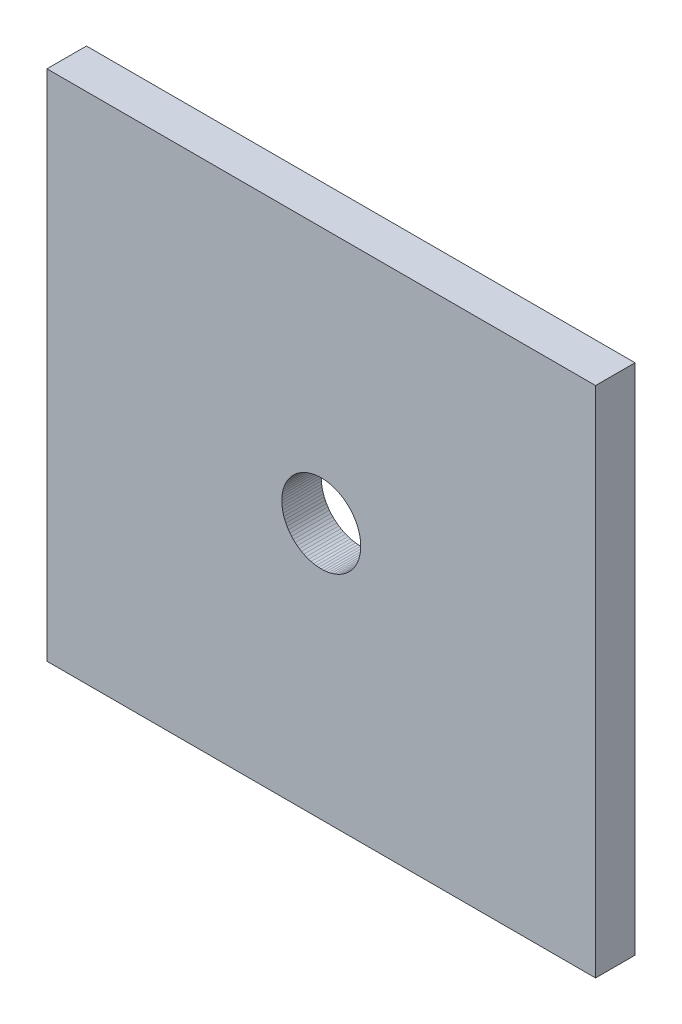
SolidWorks part; units mm, degrees
material "Plain Carbon Steel"
ref_plane "Front Plane" through (0, 0, 0) normal (0, 0, 1) x (1, 0, 0)
ref_plane "Top Plane" through (0, 0, 0) normal (0, 1, 0) x (1, 0, 0)
ref_plane "Right Plane" through (0, 0, 0) normal (1, 0, 0) x (0, 0, -1)
sketch "Model" plane through (0, 0, 0) normal (0, 0, 1) x (1, 0, 0)
  line L0 (1622.0549, -184.7379) -> (1622.2624, -184.485)
  line L1 (1617.643, -186.3984) -> (1617.9686, -186.4305)
  line L2 (1621.5924, -185.2004) -> (1621.8312, -184.9767)
  line L3 (1617.0016, -186.2708) -> (1617.3202, -186.3451)
  line L4 (1620.2091, -186.0606) -> (1620.5071, -185.9255)
  line L5 (1617.9686, -176.4519) -> (1617.643, -176.4839)
  line L6 (1613.8113, -183.6526) -> (1613.9655, -183.9412)
  line L7 (1614.7601, -184.9767) -> (1614.9989, -185.2004)
  line L8 (1617.643, -176.4839) -> (1617.3202, -176.5372)
  line L9 (1613.3917, -182.4166) -> (1613.466, -182.7353)
  line L10 (1615.7957, -177.111) -> (1615.5178, -177.2838)
  line L11 (1613.561, -183.0484) -> (1613.6763, -183.3546)
  line L12 (1621.5924, -177.682) -> (1621.3395, -177.4744)
  line L13 (1619.2711, -176.5372) -> (1618.9483, -176.4839)
  line L14 (1616.3822, -176.8218) -> (1616.0842, -176.9568)
  line L15 (1614.9989, -177.682) -> (1614.7601, -177.9056)
  line L16 (1617.3202, -186.3451) -> (1617.643, -186.3984)
  line L17 (1613.3064, -181.1142) -> (1613.2957, -181.4412)
  line L18 (1614.9989, -185.2004) -> (1615.2519, -185.4079)
  line L19 (1614.7601, -177.9056) -> (1614.5365, -178.1444)
  line L20 (1614.5365, -184.7379) -> (1614.7601, -184.9767)
  line L21 (1616.0842, -185.9255) -> (1616.3822, -186.0606)
  line L22 (1613.6763, -179.5278) -> (1613.561, -179.834)
  line L23 (1615.5178, -185.5985) -> (1615.7957, -185.7713)
  line L24 (1616.6885, -176.7065) -> (1616.3822, -176.8218)
  line L25 (1613.561, -179.834) -> (1613.466, -180.1471)
  line L26 (1618.2957, -176.4412) -> (1617.9686, -176.4519)
  line L27 (1613.6763, -183.3546) -> (1613.8113, -183.6526)
  line L28 (1614.5365, -178.1444) -> (1614.3289, -178.3974)
  line L29 (1620.2091, -176.8218) -> (1619.9029, -176.7065)
  line L30 (1618.6227, -176.4519) -> (1618.2957, -176.4412)
  line L31 (1621.0735, -177.2838) -> (1620.7957, -177.111)
  line L32 (1653.0457, -148.9412) -> (1653.0457, -213.9412)
  line L33 (1583.5457, -148.9412) -> (1653.0457, -148.9412)
  line L34 (1583.5457, -213.9412) -> (1583.5457, -148.9412)
  line L35 (1653.0457, -213.9412) -> (1583.5457, -213.9412)
  line L36 (1616.6885, -186.1758) -> (1617.0016, -186.2708)
  line L37 (1616.3822, -186.0606) -> (1616.6885, -186.1758)
  line L38 (1615.7957, -185.7713) -> (1616.0842, -185.9255)
  line L39 (1615.2519, -185.4079) -> (1615.5178, -185.5985)
  line L40 (1614.3289, -184.485) -> (1614.5365, -184.7379)
  line L41 (1614.1383, -184.219) -> (1614.3289, -184.485)
  line L42 (1613.9655, -183.9412) -> (1614.1383, -184.219)
  line L43 (1613.466, -182.7353) -> (1613.561, -183.0484)
  line L44 (1613.3384, -182.0938) -> (1613.3917, -182.4166)
  line L45 (1613.3064, -181.7682) -> (1613.3384, -182.0938)
  line L46 (1613.2957, -181.4412) -> (1613.3064, -181.7682)
  line L47 (1613.3384, -180.7885) -> (1613.3064, -181.1142)
  line L48 (1613.3917, -180.4657) -> (1613.3384, -180.7885)
  line L49 (1613.466, -180.1471) -> (1613.3917, -180.4657)
  line L50 (1613.8113, -179.2297) -> (1613.6763, -179.5278)
  line L51 (1613.9655, -178.9412) -> (1613.8113, -179.2297)
  line L52 (1614.1383, -178.6633) -> (1613.9655, -178.9412)
  line L53 (1614.3289, -178.3974) -> (1614.1383, -178.6633)
  line L54 (1615.2519, -177.4744) -> (1614.9989, -177.682)
  line L55 (1615.5178, -177.2838) -> (1615.2519, -177.4744)
  line L56 (1616.0842, -176.9568) -> (1615.7957, -177.111)
  line L57 (1617.0016, -176.6115) -> (1616.6885, -176.7065)
  line L58 (1617.3202, -176.5372) -> (1617.0016, -176.6115)
  line L59 (1618.9483, -176.4839) -> (1618.6227, -176.4519)
  line L60 (1619.5898, -176.6115) -> (1619.2711, -176.5372)
  line L61 (1619.9029, -176.7065) -> (1619.5898, -176.6115)
  line L62 (1620.5071, -176.9568) -> (1620.2091, -176.8218)
  line L63 (1620.7957, -177.111) -> (1620.5071, -176.9568)
  line L64 (1621.3395, -177.4744) -> (1621.0735, -177.2838)
  line L65 (1621.8312, -177.9056) -> (1621.5924, -177.682)
  line L66 (1622.0549, -178.1444) -> (1621.8312, -177.9056)
  line L67 (1622.2624, -178.3974) -> (1622.0549, -178.1444)
  line L68 (1622.453, -178.6633) -> (1622.2624, -178.3974)
  line L69 (1622.6258, -178.9412) -> (1622.453, -178.6633)
  line L70 (1622.78, -179.2297) -> (1622.6258, -178.9412)
  line L71 (1622.9151, -179.5278) -> (1622.78, -179.2297)
  line L72 (1623.0303, -179.834) -> (1622.9151, -179.5278)
  line L73 (1623.1253, -180.1471) -> (1623.0303, -179.834)
  line L74 (1623.1996, -180.4657) -> (1623.1253, -180.1471)
  line L75 (1623.2529, -180.7885) -> (1623.1996, -180.4657)
  line L76 (1623.285, -181.1142) -> (1623.2529, -180.7885)
  line L77 (1623.2957, -181.4412) -> (1623.285, -181.1142)
  line L78 (1623.285, -181.7682) -> (1623.2957, -181.4412)
  line L79 (1623.2529, -182.0938) -> (1623.285, -181.7682)
  line L80 (1623.1996, -182.4166) -> (1623.2529, -182.0938)
  line L81 (1623.1253, -182.7353) -> (1623.1996, -182.4166)
  line L82 (1623.0303, -183.0484) -> (1623.1253, -182.7353)
  line L83 (1622.9151, -183.3546) -> (1623.0303, -183.0484)
  line L84 (1622.78, -183.6526) -> (1622.9151, -183.3546)
  line L85 (1622.6258, -183.9412) -> (1622.78, -183.6526)
  line L86 (1622.453, -184.219) -> (1622.6258, -183.9412)
  line L87 (1622.2624, -184.485) -> (1622.453, -184.219)
  line L88 (1621.8312, -184.9767) -> (1622.0549, -184.7379)
  line L89 (1621.3395, -185.4079) -> (1621.5924, -185.2004)
  line L90 (1621.0735, -185.5985) -> (1621.3395, -185.4079)
  line L91 (1620.7957, -185.7713) -> (1621.0735, -185.5985)
  line L92 (1620.5071, -185.9255) -> (1620.7957, -185.7713)
  line L93 (1619.9029, -186.1758) -> (1620.2091, -186.0606)
  line L94 (1619.5898, -186.2708) -> (1619.9029, -186.1758)
  line L95 (1619.2711, -186.3451) -> (1619.5898, -186.2708)
  line L96 (1618.9483, -186.3984) -> (1619.2711, -186.3451)
  line L97 (1618.6227, -186.4305) -> (1618.9483, -186.3984)
  line L98 (1618.2957, -186.4412) -> (1618.6227, -186.4305)
  line L99 (1617.9686, -186.4305) -> (1618.2957, -186.4412)
  line L100 (1610.0539, -203.9412) -> (1626.5374, -203.9412)
  line L101 (1610.0539, -202.9412) -> (1610.0539, -194.3253)
  line L102 (1610.0539, -194.3253) -> (1612.0895, -194.3253)
  line L103 (1612.0895, -194.3253) -> (1612.9574, -194.3971)
  line L104 (1612.9574, -194.3971) -> (1613.6879, -194.6125)
  line L105 (1613.6879, -194.6125) -> (1614.1749, -194.9247)
  line L106 (1614.1749, -194.9247) -> (1614.2967, -195.0995)
  line L107 (1614.2967, -195.0995) -> (1614.3373, -195.2868)
  line L108 (1614.3373, -195.2868) -> (1614.3373, -201.9797)
  line L109 (1614.3373, -201.9797) -> (1614.2967, -202.1724)
  line L110 (1614.2967, -202.1724) -> (1614.1749, -202.3512)
  line L111 (1614.1749, -202.3512) -> (1613.6879, -202.6665)
  line L112 (1613.6879, -202.6665) -> (1612.9761, -202.8725)
  line L113 (1612.9761, -202.8725) -> (1612.0895, -202.9412)
  line L114 (1612.0895, -202.9412) -> (1610.0539, -202.9412)
  line L115 (1610.0539, -194.3253) -> (1610.0539, -202.9412)
  line L116 (1610.0539, -202.9412) -> (1612.0895, -202.9412)
  line L117 (1612.0895, -202.9412) -> (1612.9761, -202.8725)
  line L118 (1612.9761, -202.8725) -> (1613.6879, -202.6665)
  line L119 (1613.6879, -202.6665) -> (1614.1749, -202.3512)
  line L120 (1614.1749, -202.3512) -> (1614.2967, -202.1724)
  line L121 (1614.2967, -202.1724) -> (1614.3373, -201.9797)
  line L122 (1614.3373, -201.9797) -> (1614.3373, -195.2868)
  line L123 (1614.3373, -195.2868) -> (1614.2967, -195.0995)
  line L124 (1614.2967, -195.0995) -> (1614.1749, -194.9247)
  line L125 (1614.1749, -194.9247) -> (1613.6879, -194.6125)
  line L126 (1613.6879, -194.6125) -> (1612.9574, -194.3971)
  line L127 (1612.9574, -194.3971) -> (1612.0895, -194.3253)
  line L128 (1612.0895, -194.3253) -> (1610.0539, -194.3253)
  line L129 (1616.0479, -202.9412) -> (1616.0479, -198.5455)
  line L130 (1616.0479, -198.5455) -> (1618.0834, -198.5455)
  line L131 (1618.0834, -198.5455) -> (1619.1979, -198.6828)
  line L132 (1619.1979, -198.6828) -> (1619.8691, -198.8951)
  line L133 (1619.8691, -198.8951) -> (1620.2157, -199.1636)
  line L134 (1620.2157, -199.1636) -> (1620.3312, -199.4696)
  line L135 (1620.3312, -199.4696) -> (1620.3312, -201.9796)
  line L136 (1620.3312, -201.9796) -> (1620.2898, -202.177)
  line L137 (1620.2898, -202.177) -> (1620.1657, -202.3573)
  line L138 (1620.1657, -202.3573) -> (1619.6693, -202.6664)
  line L139 (1619.6693, -202.6664) -> (1618.9481, -202.8725)
  line L140 (1618.9481, -202.8725) -> (1618.0834, -202.9412)
  line L141 (1618.0834, -202.9412) -> (1616.0479, -202.9412)
  line L142 (1616.0479, -194.3253) -> (1616.0479, -202.9412)
  line L143 (1616.0479, -202.9412) -> (1618.0834, -202.9412)
  line L144 (1618.0834, -202.9412) -> (1618.9481, -202.8725)
  line L145 (1618.9481, -202.8725) -> (1619.6693, -202.6665)
  line L146 (1619.6693, -202.6665) -> (1620.1657, -202.3574)
  line L147 (1620.1657, -202.3574) -> (1620.2898, -202.1771)
  line L148 (1620.2898, -202.1771) -> (1620.3312, -201.9797)
  line L149 (1620.3312, -201.9797) -> (1620.3312, -199.4698)
  line L150 (1620.3312, -199.4698) -> (1620.2157, -199.164)
  line L151 (1620.2157, -199.164) -> (1619.8691, -198.8955)
  line L152 (1619.8691, -198.8955) -> (1619.1979, -198.6832)
  line L153 (1619.1979, -198.6832) -> (1618.0834, -198.5459)
  line L154 (1618.0834, -198.5459) -> (1619.1854, -198.4179)
  line L155 (1619.1854, -198.4179) -> (1619.8691, -198.2087)
  line L156 (1619.8691, -198.2087) -> (1620.2157, -197.9309)
  line L157 (1620.2157, -197.9309) -> (1620.3312, -197.6218)
  line L158 (1620.3312, -197.6218) -> (1620.3312, -195.2868)
  line L159 (1620.3312, -195.2868) -> (1620.2898, -195.0995)
  line L160 (1620.2898, -195.0995) -> (1620.1657, -194.9247)
  line L161 (1620.1657, -194.9247) -> (1619.6693, -194.6125)
  line L162 (1619.6693, -194.6125) -> (1618.9419, -194.3971)
  line L163 (1618.9419, -194.3971) -> (1618.0834, -194.3253)
  line L164 (1618.0834, -194.3253) -> (1616.0479, -194.3253)
  line L165 (1618.0834, -198.5463) -> (1616.0479, -198.5463)
  line L166 (1616.0479, -198.5463) -> (1616.0479, -194.3253)
  line L167 (1616.0479, -194.3253) -> (1618.0834, -194.3253)
  line L168 (1618.0834, -194.3253) -> (1618.9419, -194.3971)
  line L169 (1618.9419, -194.3971) -> (1619.6693, -194.6126)
  line L170 (1619.6693, -194.6126) -> (1620.1657, -194.9248)
  line L171 (1620.1657, -194.9248) -> (1620.2898, -195.0996)
  line L172 (1620.2898, -195.0996) -> (1620.3312, -195.2869)
  line L173 (1620.3312, -195.2869) -> (1620.3312, -197.6221)
  line L174 (1620.3312, -197.6221) -> (1620.2157, -197.9312)
  line L175 (1620.2157, -197.9312) -> (1619.8691, -198.2091)
  line L176 (1619.8691, -198.2091) -> (1619.1854, -198.4182)
  line L177 (1619.1854, -198.4182) -> (1618.0834, -198.5463)
  line L178 (1624.2896, -202.9412) -> (1623.4076, -202.8709)
  line L179 (1623.4076, -202.8709) -> (1622.6849, -202.6602)
  line L180 (1622.6849, -202.6602) -> (1622.2025, -202.3496)
  line L181 (1622.2025, -202.3496) -> (1622.0819, -202.172)
  line L182 (1622.0819, -202.172) -> (1622.0418, -201.9797)
  line L183 (1622.0418, -201.9797) -> (1622.0819, -202.172)
  line L184 (1622.0819, -202.172) -> (1622.2025, -202.3496)
  line L185 (1622.2025, -202.3496) -> (1622.6849, -202.6602)
  line L186 (1625.8943, -202.6602) -> (1626.3766, -202.3496)
  line L187 (1626.3766, -202.3496) -> (1626.4972, -202.172)
  line L188 (1626.4972, -202.172) -> (1626.5374, -201.9797)
  line L189 (1626.5374, -201.9797) -> (1626.5374, -198.5584)
  line L190 (1626.5374, -198.5584) -> (1626.4972, -198.3659)
  line L191 (1626.4972, -198.3659) -> (1626.3766, -198.1884)
  line L192 (1626.3766, -198.1884) -> (1625.8943, -197.8777)
  line L193 (1625.8943, -197.8777) -> (1625.1715, -197.667)
  line L194 (1625.1715, -197.667) -> (1624.2896, -197.5968)
  line L195 (1624.2896, -197.5968) -> (1622.9409, -197.7966)
  line L196 (1622.9409, -197.7966) -> (1622.4788, -198.0495)
  line L197 (1622.4788, -198.0495) -> (1622.0418, -198.5584)
  line L198 (1622.0418, -198.5584) -> (1622.0418, -194.3253)
  line L199 (1622.0418, -194.3253) -> (1626.3875, -194.3253)
  line L200 (1626.3875, -194.3253) -> (1622.0418, -194.3253)
  line L201 (1622.0418, -194.3253) -> (1622.0418, -198.5584)
  line L202 (1622.0418, -198.5584) -> (1622.4788, -198.0495)
  line L203 (1622.4788, -198.0495) -> (1622.9409, -197.7966)
  line L204 (1622.9409, -197.7966) -> (1624.2896, -197.5968)
  line L205 (1624.2896, -197.5968) -> (1625.1715, -197.667)
  line L206 (1625.1715, -197.667) -> (1625.8943, -197.8777)
  line L207 (1625.8943, -197.8777) -> (1626.3766, -198.1884)
  line L208 (1626.3766, -198.1884) -> (1626.4972, -198.3659)
  line L209 (1626.4972, -198.3659) -> (1626.5374, -198.5584)
  line L210 (1626.5374, -198.5584) -> (1626.5374, -201.9797)
  line L211 (1626.5374, -201.9797) -> (1626.4972, -202.172)
  line L212 (1626.4972, -202.172) -> (1626.3766, -202.3496)
  line L213 (1626.3766, -202.3496) -> (1625.8943, -202.6602)
  line L214 (1625.8943, -202.6602) -> (1625.1715, -202.8709)
  line L215 (1625.1715, -202.8709) -> (1624.2896, -202.9412)
sketch "Sketch1" plane through (0, 0, 0) normal (0, 0, 1) x (1, 0, 0)
  line L0 (1583.5457, -213.9412) -> (1583.5457, -148.9412) construction
  line L1 (1653.0457, -213.9412) -> (1583.5457, -213.9412) construction
  line L2 (1653.0457, -148.9412) -> (1653.0457, -213.9412) construction
  line L3 (1583.5457, -148.9412) -> (1653.0457, -148.9412) construction
  line L4 (1583.5457, -213.9412) -> (1583.5457, -148.9412)
  line L5 (1653.0457, -213.9412) -> (1583.5457, -213.9412)
  line L6 (1653.0457, -148.9412) -> (1653.0457, -213.9412)
  line L7 (1583.5457, -148.9412) -> (1653.0457, -148.9412)
  line L8 (1620.7957, -177.111) -> (1620.5071, -176.9568) construction
  line L9 (1621.0735, -177.2838) -> (1620.7957, -177.111) construction
  line L10 (1621.3395, -177.4744) -> (1621.0735, -177.2838) construction
  line L11 (1621.5924, -177.682) -> (1621.3395, -177.4744) construction
  line L12 (1621.8312, -177.9056) -> (1621.5924, -177.682) construction
  line L13 (1622.0549, -178.1444) -> (1621.8312, -177.9056) construction
  line L14 (1622.2624, -178.3974) -> (1622.0549, -178.1444) construction
  line L15 (1622.453, -178.6633) -> (1622.2624, -178.3974) construction
  line L16 (1622.6258, -178.9412) -> (1622.453, -178.6633) construction
  line L17 (1622.78, -179.2297) -> (1622.6258, -178.9412) construction
  line L18 (1622.9151, -179.5278) -> (1622.78, -179.2297) construction
  line L19 (1623.0303, -179.834) -> (1622.9151, -179.5278) construction
  line L20 (1623.1253, -180.1471) -> (1623.0303, -179.834) construction
  line L21 (1623.1996, -180.4657) -> (1623.1253, -180.1471) construction
  line L22 (1623.2529, -180.7885) -> (1623.1996, -180.4657) construction
  line L23 (1623.285, -181.1142) -> (1623.2529, -180.7885) construction
  line L24 (1623.2957, -181.4412) -> (1623.285, -181.1142) construction
  line L25 (1623.285, -181.7682) -> (1623.2957, -181.4412) construction
  line L26 (1623.2529, -182.0938) -> (1623.285, -181.7682) construction
  line L27 (1623.1996, -182.4166) -> (1623.2529, -182.0938) construction
  line L28 (1623.1253, -182.7353) -> (1623.1996, -182.4166) construction
  line L29 (1623.0303, -183.0484) -> (1623.1253, -182.7353) construction
  line L30 (1622.9151, -183.3546) -> (1623.0303, -183.0484) construction
  line L31 (1622.78, -183.6526) -> (1622.9151, -183.3546) construction
  line L32 (1622.6258, -183.9412) -> (1622.78, -183.6526) construction
  line L33 (1622.453, -184.219) -> (1622.6258, -183.9412) construction
  line L34 (1622.2624, -184.485) -> (1622.453, -184.219) construction
  line L35 (1622.0549, -184.7379) -> (1622.2624, -184.485) construction
  line L36 (1621.8312, -184.9767) -> (1622.0549, -184.7379) construction
  line L37 (1621.5924, -185.2004) -> (1621.8312, -184.9767) construction
  line L38 (1621.3395, -185.4079) -> (1621.5924, -185.2004) construction
  line L39 (1621.0735, -185.5985) -> (1621.3395, -185.4079) construction
  line L40 (1620.7957, -185.7713) -> (1621.0735, -185.5985) construction
  line L41 (1620.5071, -185.9255) -> (1620.7957, -185.7713) construction
  line L42 (1620.2091, -186.0606) -> (1620.5071, -185.9255) construction
  line L43 (1619.9029, -186.1758) -> (1620.2091, -186.0606) construction
  line L44 (1619.5898, -186.2708) -> (1619.9029, -186.1758) construction
  line L45 (1619.2711, -186.3451) -> (1619.5898, -186.2708) construction
  line L46 (1618.9483, -186.3984) -> (1619.2711, -186.3451) construction
  line L47 (1618.6227, -186.4305) -> (1618.9483, -186.3984) construction
  line L48 (1618.2957, -186.4412) -> (1618.6227, -186.4305) construction
  line L49 (1617.9686, -186.4305) -> (1618.2957, -186.4412) construction
  line L50 (1617.643, -186.3984) -> (1617.9686, -186.4305) construction
  line L51 (1617.3202, -186.3451) -> (1617.643, -186.3984) construction
  line L52 (1617.0016, -186.2708) -> (1617.3202, -186.3451) construction
  line L53 (1616.6885, -186.1758) -> (1617.0016, -186.2708) construction
  line L54 (1616.3822, -186.0606) -> (1616.6885, -186.1758) construction
  line L55 (1616.0842, -185.9255) -> (1616.3822, -186.0606) construction
  line L56 (1615.7957, -185.7713) -> (1616.0842, -185.9255) construction
  line L57 (1615.5178, -185.5985) -> (1615.7957, -185.7713) construction
  line L58 (1615.2519, -185.4079) -> (1615.5178, -185.5985) construction
  line L59 (1614.9989, -185.2004) -> (1615.2519, -185.4079) construction
  line L60 (1614.7601, -184.9767) -> (1614.9989, -185.2004) construction
  line L61 (1614.5365, -184.7379) -> (1614.7601, -184.9767) construction
  line L62 (1614.3289, -184.485) -> (1614.5365, -184.7379) construction
  line L63 (1614.1383, -184.219) -> (1614.3289, -184.485) construction
  line L64 (1613.9655, -183.9412) -> (1614.1383, -184.219) construction
  line L65 (1613.8113, -183.6526) -> (1613.9655, -183.9412) construction
  line L66 (1613.6763, -183.3546) -> (1613.8113, -183.6526) construction
  line L67 (1613.561, -183.0484) -> (1613.6763, -183.3546) construction
  line L68 (1613.466, -182.7353) -> (1613.561, -183.0484) construction
  line L69 (1613.3917, -182.4166) -> (1613.466, -182.7353) construction
  line L70 (1613.3384, -182.0938) -> (1613.3917, -182.4166) construction
  line L71 (1613.3064, -181.7682) -> (1613.3384, -182.0938) construction
  line L72 (1613.2957, -181.4412) -> (1613.3064, -181.7682) construction
  line L73 (1613.3064, -181.1142) -> (1613.2957, -181.4412) construction
  line L74 (1613.3384, -180.7885) -> (1613.3064, -181.1142) construction
  line L75 (1613.3917, -180.4657) -> (1613.3384, -180.7885) construction
  line L76 (1613.466, -180.1471) -> (1613.3917, -180.4657) construction
  line L77 (1613.561, -179.834) -> (1613.466, -180.1471) construction
  line L78 (1613.6763, -179.5278) -> (1613.561, -179.834) construction
  line L79 (1613.8113, -179.2297) -> (1613.6763, -179.5278) construction
  line L80 (1613.9655, -178.9412) -> (1613.8113, -179.2297) construction
  line L81 (1614.1383, -178.6633) -> (1613.9655, -178.9412) construction
  line L82 (1614.3289, -178.3974) -> (1614.1383, -178.6633) construction
  line L83 (1614.5365, -178.1444) -> (1614.3289, -178.3974) construction
  line L84 (1614.7601, -177.9056) -> (1614.5365, -178.1444) construction
  line L85 (1614.9989, -177.682) -> (1614.7601, -177.9056) construction
  line L86 (1615.2519, -177.4744) -> (1614.9989, -177.682) construction
  line L87 (1615.5178, -177.2838) -> (1615.2519, -177.4744) construction
  line L88 (1615.7957, -177.111) -> (1615.5178, -177.2838) construction
  line L89 (1616.0842, -176.9568) -> (1615.7957, -177.111) construction
  line L90 (1616.3822, -176.8218) -> (1616.0842, -176.9568) construction
  line L91 (1616.6885, -176.7065) -> (1616.3822, -176.8218) construction
  line L92 (1617.0016, -176.6115) -> (1616.6885, -176.7065) construction
  line L93 (1617.3202, -176.5372) -> (1617.0016, -176.6115) construction
  line L94 (1617.643, -176.4839) -> (1617.3202, -176.5372) construction
  line L95 (1617.9686, -176.4519) -> (1617.643, -176.4839) construction
  line L96 (1618.2957, -176.4412) -> (1617.9686, -176.4519) construction
  line L97 (1618.6227, -176.4519) -> (1618.2957, -176.4412) construction
  line L98 (1618.9483, -176.4839) -> (1618.6227, -176.4519) construction
  line L99 (1619.2711, -176.5372) -> (1618.9483, -176.4839) construction
  line L100 (1619.5898, -176.6115) -> (1619.2711, -176.5372) construction
  line L101 (1619.9029, -176.7065) -> (1619.5898, -176.6115) construction
  line L102 (1620.2091, -176.8218) -> (1619.9029, -176.7065) construction
  line L103 (1620.5071, -176.9568) -> (1620.2091, -176.8218) construction
  line L104 (1620.7957, -177.111) -> (1620.5071, -176.9568)
  line L105 (1621.0735, -177.2838) -> (1620.7957, -177.111)
  line L106 (1621.3395, -177.4744) -> (1621.0735, -177.2838)
  line L107 (1621.5924, -177.682) -> (1621.3395, -177.4744)
  line L108 (1621.8312, -177.9056) -> (1621.5924, -177.682)
  line L109 (1622.0549, -178.1444) -> (1621.8312, -177.9056)
  line L110 (1622.2624, -178.3974) -> (1622.0549, -178.1444)
  line L111 (1622.453, -178.6633) -> (1622.2624, -178.3974)
  line L112 (1622.6258, -178.9412) -> (1622.453, -178.6633)
  line L113 (1622.78, -179.2297) -> (1622.6258, -178.9412)
  line L114 (1622.9151, -179.5278) -> (1622.78, -179.2297)
  line L115 (1623.0303, -179.834) -> (1622.9151, -179.5278)
  line L116 (1623.1253, -180.1471) -> (1623.0303, -179.834)
  line L117 (1623.1996, -180.4657) -> (1623.1253, -180.1471)
  line L118 (1623.2529, -180.7885) -> (1623.1996, -180.4657)
  line L119 (1623.285, -181.1142) -> (1623.2529, -180.7885)
  line L120 (1623.2957, -181.4412) -> (1623.285, -181.1142)
  line L121 (1623.285, -181.7682) -> (1623.2957, -181.4412)
  line L122 (1623.2529, -182.0938) -> (1623.285, -181.7682)
  line L123 (1623.1996, -182.4166) -> (1623.2529, -182.0938)
  line L124 (1623.1253, -182.7353) -> (1623.1996, -182.4166)
  line L125 (1623.0303, -183.0484) -> (1623.1253, -182.7353)
  line L126 (1622.9151, -183.3546) -> (1623.0303, -183.0484)
  line L127 (1622.78, -183.6526) -> (1622.9151, -183.3546)
  line L128 (1622.6258, -183.9412) -> (1622.78, -183.6526)
  line L129 (1622.453, -184.219) -> (1622.6258, -183.9412)
  line L130 (1622.2624, -184.485) -> (1622.453, -184.219)
  line L131 (1622.0549, -184.7379) -> (1622.2624, -184.485)
  line L132 (1621.8312, -184.9767) -> (1622.0549, -184.7379)
  line L133 (1621.5924, -185.2004) -> (1621.8312, -184.9767)
  line L134 (1621.3395, -185.4079) -> (1621.5924, -185.2004)
  line L135 (1621.0735, -185.5985) -> (1621.3395, -185.4079)
  line L136 (1620.7957, -185.7713) -> (1621.0735, -185.5985)
  line L137 (1620.5071, -185.9255) -> (1620.7957, -185.7713)
  line L138 (1620.2091, -186.0606) -> (1620.5071, -185.9255)
  line L139 (1619.9029, -186.1758) -> (1620.2091, -186.0606)
  line L140 (1619.5898, -186.2708) -> (1619.9029, -186.1758)
  line L141 (1619.2711, -186.3451) -> (1619.5898, -186.2708)
  line L142 (1618.9483, -186.3984) -> (1619.2711, -186.3451)
  line L143 (1618.6227, -186.4305) -> (1618.9483, -186.3984)
  line L144 (1618.2957, -186.4412) -> (1618.6227, -186.4305)
  line L145 (1617.9686, -186.4305) -> (1618.2957, -186.4412)
  line L146 (1617.643, -186.3984) -> (1617.9686, -186.4305)
  line L147 (1617.3202, -186.3451) -> (1617.643, -186.3984)
  line L148 (1617.0016, -186.2708) -> (1617.3202, -186.3451)
  line L149 (1616.6885, -186.1758) -> (1617.0016, -186.2708)
  line L150 (1616.3822, -186.0606) -> (1616.6885, -186.1758)
  line L151 (1616.0842, -185.9255) -> (1616.3822, -186.0606)
  line L152 (1615.7957, -185.7713) -> (1616.0842, -185.9255)
  line L153 (1615.5178, -185.5985) -> (1615.7957, -185.7713)
  line L154 (1615.2519, -185.4079) -> (1615.5178, -185.5985)
  line L155 (1614.9989, -185.2004) -> (1615.2519, -185.4079)
  line L156 (1614.7601, -184.9767) -> (1614.9989, -185.2004)
  line L157 (1614.5365, -184.7379) -> (1614.7601, -184.9767)
  line L158 (1614.3289, -184.485) -> (1614.5365, -184.7379)
  line L159 (1614.1383, -184.219) -> (1614.3289, -184.485)
  line L160 (1613.9655, -183.9412) -> (1614.1383, -184.219)
  line L161 (1613.8113, -183.6526) -> (1613.9655, -183.9412)
  line L162 (1613.6763, -183.3546) -> (1613.8113, -183.6526)
  line L163 (1613.561, -183.0484) -> (1613.6763, -183.3546)
  line L164 (1613.466, -182.7353) -> (1613.561, -183.0484)
  line L165 (1613.3917, -182.4166) -> (1613.466, -182.7353)
  line L166 (1613.3384, -182.0938) -> (1613.3917, -182.4166)
  line L167 (1613.3064, -181.7682) -> (1613.3384, -182.0938)
  line L168 (1613.2957, -181.4412) -> (1613.3064, -181.7682)
  line L169 (1613.3064, -181.1142) -> (1613.2957, -181.4412)
  line L170 (1613.3384, -180.7885) -> (1613.3064, -181.1142)
  line L171 (1613.3917, -180.4657) -> (1613.3384, -180.7885)
  line L172 (1613.466, -180.1471) -> (1613.3917, -180.4657)
  line L173 (1613.561, -179.834) -> (1613.466, -180.1471)
  line L174 (1613.6763, -179.5278) -> (1613.561, -179.834)
  line L175 (1613.8113, -179.2297) -> (1613.6763, -179.5278)
  line L176 (1613.9655, -178.9412) -> (1613.8113, -179.2297)
  line L177 (1614.1383, -178.6633) -> (1613.9655, -178.9412)
  line L178 (1614.3289, -178.3974) -> (1614.1383, -178.6633)
  line L179 (1614.5365, -178.1444) -> (1614.3289, -178.3974)
  line L180 (1614.7601, -177.9056) -> (1614.5365, -178.1444)
  line L181 (1614.9989, -177.682) -> (1614.7601, -177.9056)
  line L182 (1615.2519, -177.4744) -> (1614.9989, -177.682)
  line L183 (1615.5178, -177.2838) -> (1615.2519, -177.4744)
  line L184 (1615.7957, -177.111) -> (1615.5178, -177.2838)
  line L185 (1616.0842, -176.9568) -> (1615.7957, -177.111)
  line L186 (1616.3822, -176.8218) -> (1616.0842, -176.9568)
  line L187 (1616.6885, -176.7065) -> (1616.3822, -176.8218)
  line L188 (1617.0016, -176.6115) -> (1616.6885, -176.7065)
  line L189 (1617.3202, -176.5372) -> (1617.0016, -176.6115)
  line L190 (1617.643, -176.4839) -> (1617.3202, -176.5372)
  line L191 (1617.9686, -176.4519) -> (1617.643, -176.4839)
  line L192 (1618.2957, -176.4412) -> (1617.9686, -176.4519)
  line L193 (1618.6227, -176.4519) -> (1618.2957, -176.4412)
  line L194 (1618.9483, -176.4839) -> (1618.6227, -176.4519)
  line L195 (1619.2711, -176.5372) -> (1618.9483, -176.4839)
  line L196 (1619.5898, -176.6115) -> (1619.2711, -176.5372)
  line L197 (1619.9029, -176.7065) -> (1619.5898, -176.6115)
  line L198 (1620.2091, -176.8218) -> (1619.9029, -176.7065)
  line L199 (1620.5071, -176.9568) -> (1620.2091, -176.8218)
extrude "Boss-Extrude1" add sketch "Sketch1" along normal mid plane 5
sketch "Sketch2" plane through (0, 0, 2.5) normal (0, 0, 1) x (1, 0, 0)
  circle A0 centre (1618.2957, -181.4412) radius 5
ref_axis "Axis1" through (1618.2957, -181.4412, 2.5) along (0, 0, 1)
